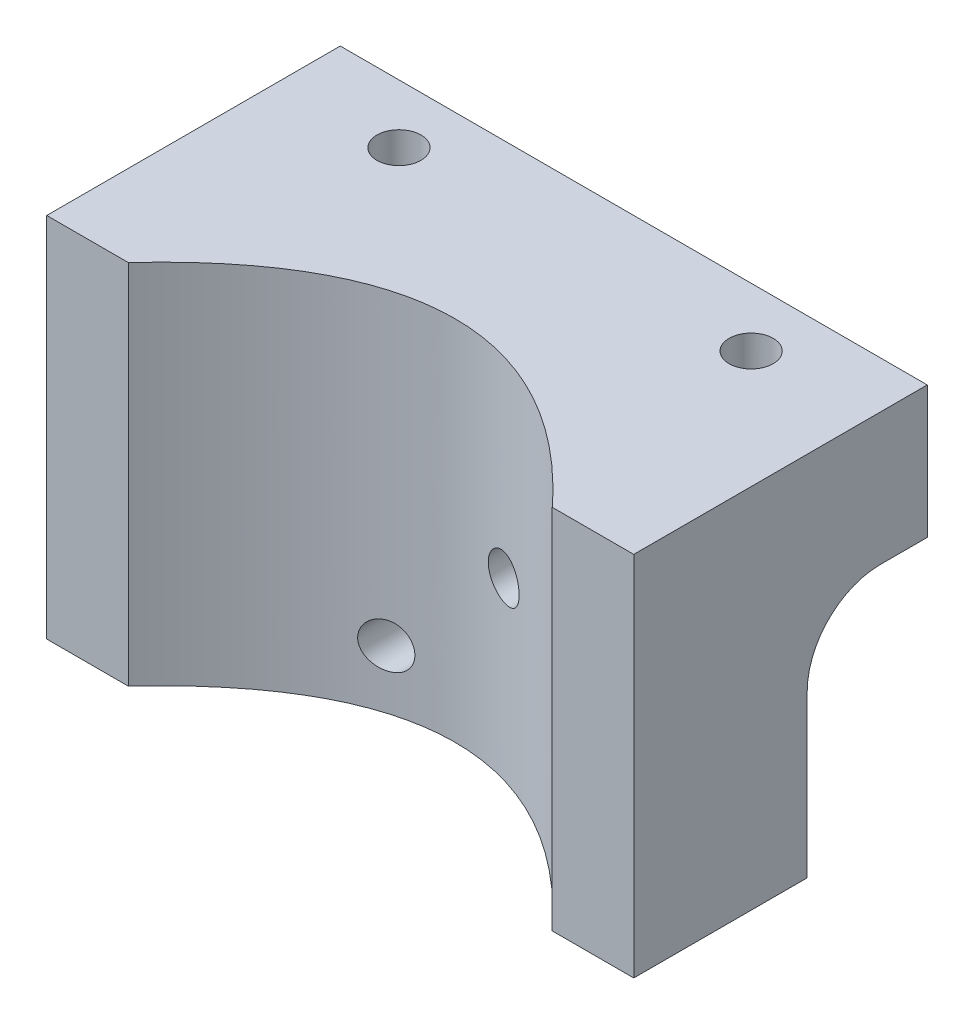
SolidWorks part; units mm, degrees
ref_plane "Front Plane" through (0, 0, 0) normal (0, 0, 1) x (1, 0, 0)
ref_plane "Top Plane" through (0, 0, 0) normal (0, 1, 0) x (1, 0, 0)
ref_plane "Right Plane" through (0, 0, 0) normal (1, 0, 0) x (0, 0, -1)
sketch "Sketch1" plane through (0, 0, 0) normal (0, 1, 0) x (1, 0, 0)
  line L0 (0, 0) -> (-5.555, 0)
  line L1 (0, 0) -> (28.89, 0)
  line L5 (28.89, 0) -> (34.445, 0)
  line L7 (-5.555, 0) -> (-5.555, 11.82)
  line L8 (-5.555, 11.82) -> (15.89, 11.82)
  line L9 (34.445, 11.82) -> (34.445, 0)
  line L10 (15.89, 11.82) -> (34.445, 11.82)
  spline S0 degree 2 poles (0, 0) (14.445, 15.64) (28.89, 0) knots 0 0 0 1 1 1
extrude "Boss-Extrude1" add sketch "Sketch1" along normal blind 25 contours L0 S0 L5 L9 L10 L8 L7 region at (-2.7775, 0, -0.4171)
sketch "Sketch2" plane through (0, 0, -11.82) normal (0, 0, -1) x (-1, 0, 0)
  line L0 (-34.445, 25) -> (-34.445, 0) construction
  line L1 (5.555, 25) -> (-34.445, 25)
  line L2 (5.555, 25) -> (5.555, 16)
  line L3 (5.555, 16) -> (-34.445, 16)
  line L4 (-34.445, 25) -> (-34.445, 16)
extrude "Boss-Extrude2" add sketch "Sketch2" along normal blind 8.18
sketch "Sketch3" plane through (0, 0, -11.82) normal (0, 0, -1) x (-1, 0, 0)
  line L0 (-14.445, 0) -> (-14.445, 16)
  line L1 (5.555, 0) -> (-34.445, 0) construction
  line L2 (-34.445, 16) -> (5.555, 16) construction
  line L3 (-14.445, 0) -> (-10.445, 0)
  line L4 (-10.445, 0) -> (-10.445, 4)
  line L5 (-14.445, 16) -> (-18.445, 16)
  line L6 (-18.445, 16) -> (-18.445, 12)
  circle A0 centre (-10.445, 4) radius 1.5
  circle A1 centre (-10.445, 4) radius 3.75
  circle A2 centre (-18.445, 12) radius 1.5
  circle A3 centre (-18.445, 12) radius 3.75
  dimension "D1" = 3
  dimension "D2" = 7.5
  dimension "D3" = 4
  dimension "D4" = 4
fillet "Fillet1" radius 5 1 edges at (14.445, 16, -11.82)
extrude "Cut-Extrude1" cut sketch "Sketch3" against normal through all both and the other way through all contours A2 | A0 region at (17.4143, 13.0307, -11.82) region at (11.4757, 5.0307, -11.82)
extrude "Cut-Extrude2" cut sketch "Sketch3<3>" along normal through all contours A3 A2 | A1 A0 region at (15.8683, 14.5767, -11.82) region at (13.0217, 6.5767, -11.82)
sketch "Sketch3<3>" plane through (0, 0, -11.82) normal (0, 0, -1) x (-1, 0, 0) same geometry as "Sketch3"
sketch "Sketch4" plane through (0, 25, 0) normal (0, 1, 0) x (1, 0, 0)
  line L0 (14.445, 20) -> (14.445, 16)
  line L1 (-5.555, 20) -> (34.445, 20) construction
  line L2 (14.445, 16) -> (2.445, 16)
  line L3 (14.445, 16) -> (26.445, 16)
  circle A0 centre (26.445, 16) radius 1.5
  circle A1 centre (2.445, 16) radius 1.5
  circle A2 centre (26.445, 16) radius 4
  circle A3 centre (2.445, 16) radius 4
  dimension "D1" = 3
  dimension "D4" = 8
  dimension "D2" = 4
  dimension "D3" = 12
extrude "Cut-Extrude3" cut sketch "Sketch4" against normal through all contours A0 | A1 region at (0.9874, 25, -16) region at (26.445, 25, -17.4576)
extrude "Cut-Extrude9" cut sketch "Sketch4<4>" against normal through all from surface contours A2 A0 | A3 A1 region at (-1.4419, 25, -16) region at (26.445, 25, -19.8869) starting at face at (14.445, 16, -17.785)
sketch "Sketch4<4>" plane through (0, 25, 0) normal (0, 1, 0) x (1, 0, 0) same geometry as "Sketch4"
